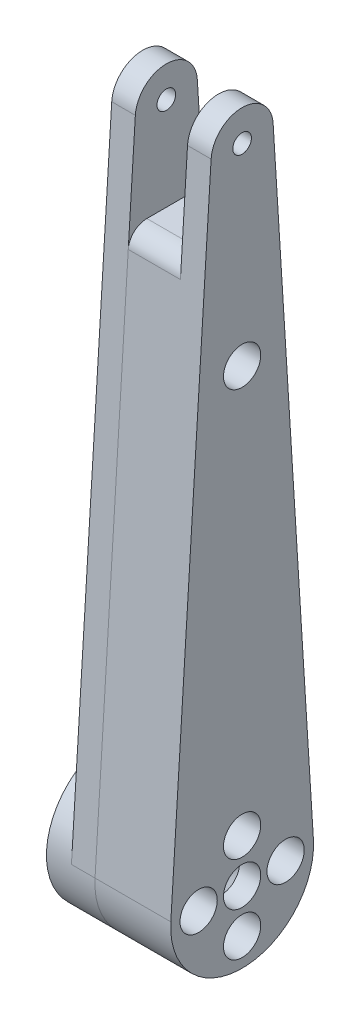
SolidWorks part; units mm, degrees
note: The reader was unsure of these and kept them because the rebuilt part matched: shared geometry of "Sketch1<4>", "Sketch1<5>".
ref_plane "Front Plane" through (0, 0, 0) normal (0, 0, 1) x (1, 0, 0)
ref_plane "Top Plane" through (0, 0, 0) normal (0, 1, 0) x (1, 0, 0)
ref_plane "Right Plane" through (0, 0, 0) normal (1, 0, 0) x (0, 0, -1)
sketch "Sketch1" plane through (0, 0, 0) normal (1, 0, 0) x (0, 0, -1)
  line L0 (11.4773, 0.7222) -> (4.9901, 103.814)
  line L1 (-4.9901, 103.814) -> (-11.4773, 0.7222)
  circle A0 centre (0, 0) radius 11.5
  circle A1 centre (0, 103.5) radius 5
  circle A2 centre (0, 0) radius 10.25
  circle A3 centre (0, 103.5) radius 1.5
  circle A4 centre (0, 0) radius 1.7
  dimension "D1" = 10
  dimension "D2" = 23
  dimension "D4" = 20.5
  dimension "D5" = 3.4
  dimension "D6" = 3
  dimension "D3" = 103.5
extrude "Boss-Extrude1" add sketch "Sketch1" along normal blind 16 contours A1 | A1 L1 A0 L0 | A0 A2 | A2
extrude "Boss-Extrude2" add sketch "Sketch1<4>" against normal blind 4 contours A0 A2
sketch "Sketch1<4>" plane through (0, 0, 0) normal (1, 0, 0) x (0, 0, -1) same geometry as "Sketch1"
extrude "Boss-Extrude3" add sketch "Sketch1<5>" against normal blind 2 contours A2 A4
sketch "Sketch1<5>" plane through (0, 0, 0) normal (1, 0, 0) x (0, 0, -1) same geometry as "Sketch1"
hole_wizard "CBORE for M3 Hex Socket Head Cap Screw1" positions "Sketch2" profile "Sketch3" counterbore size "M3" standard "ISO" end condition through all
sketch "Sketch2" plane through (16, 0, 0) normal (1, 0, 0) x (0, 0, -1)
  point P0 (0, 7)
  dimension "D1" = 7
sketch "Sketch3" plane through (16, 7, 0) normal (0, 1, 0) x (0, 0, -1)
  line L0 (0, 0) -> (0, 20)
  line L1 (0, 20) -> (1.7, 20)
  line L3 (1.7, 20) -> (1.7, 9.2)
  line L4 (1.7, 9.2) -> (3, 9.2)
  line L5 (3, 9.2) -> (3, 0)
  line L7 (3, 0) -> (0, 0)
  line L11 (0, -6.35) -> (0, 107.95) construction
  dimension "Thru Hole Dia." = 3.4
  dimension "Thru Hole Depth" = 20
  dimension "C'Bore Dia." = 6
  dimension "C'Bore Depth" = 9.2
chamfer "Chamfer1" distance 1.3 distance2 1.3 1 edges at (6.8, 7, -3)
pattern_circular "CirPattern2" count 4 over 360 about axis through (0, 0, 0) along (1, 0, 0) of "CBORE for M3 Hex Socket Head Cap Screw1", "Chamfer1"
sketch "Sketch4" plane through (16, 0, 0) normal (1, 0, 0) x (0, 0, -1)
  circle A0 centre (0, 0) radius 3
  circle A2 centre (0, 7) radius 3 construction
extrude "Cut-Extrude2" cut sketch "Sketch4" against normal blind 4.7
chamfer "Chamfer2" distance 1.3 distance2 1.3 1 edges at (11.3, 0, -3)
sketch "Sketch6" plane through (0, 0, 0) normal (0, 0, 1) x (1, 0, 0)
  line L1 (3.8, 108.5) -> (12.2, 108.5)
  line L2 (3.8, 108.5) -> (3.8, 88.5)
  line L3 (3.8, 88.5) -> (12.2, 88.5)
  line L4 (12.2, 108.5) -> (12.2, 88.5)
  line L5 (16, 108.5) -> (0, 108.5) construction
  point P8 (8, 108.5)
  dimension "D1" = 8.4
  dimension "D2" = 20
extrude "Cut-Extrude5" cut sketch "Sketch6" against normal through all both and the other way through all
fillet "Fillet1" radius 3 2 edges at (8, 88.5, -5.9538) (8, 88.5, 5.9538)
ref_plane "Plane1" through (3.8, 0, 0) normal (1, 0, 0) x (0, 0, -1)
split "Split1" trim tools "Plane1" bodies to split 111 resulting bodies 112 113
hole_wizard "CBORE for M3 Hex Socket Head Cap Screw2" positions "Sketch7" profile "Sketch8" counterbore size "M3" standard "ISO" end condition through all
sketch "Sketch7" plane through (16, 0, 0) normal (1, 0, 0) x (0, 0, -1)
  line L0 (3.1366, 88.5) -> (-3.1366, 88.5) construction
  point P0 (0, 72.5)
  dimension "D1" = 16
sketch "Sketch8" plane through (16, 72.5, 0) normal (0, 1, 0) x (0, 0, -1)
  line L0 (0, 0) -> (0, 20)
  line L1 (0, 20) -> (1.5, 20)
  line L3 (1.5, 20) -> (1.5, 8)
  line L4 (1.5, 8) -> (3, 8)
  line L5 (3, 8) -> (3, 0)
  line L7 (3, 0) -> (0, 0)
  line L11 (0, -6.35) -> (0, 107.95) construction
  dimension "Thru Hole Dia." = 3
  dimension "Thru Hole Depth" = 20
  dimension "C'Bore Dia." = 6
  dimension "C'Bore Depth" = 8
sketch "Sketch9" plane through (8, 0, 0) normal (1, 0, 0) x (0, 0, -1)
  circle A3 centre (0, 72.5) radius 1.7
  dimension "D1" = 3.4
extrude "Cut-Extrude6" cut sketch "Sketch9" against normal through all
chamfer "Chamfer3" distance 1.3 distance2 1.3 1 edges at (8, 72.5, -3)
other "Save Bodies1"
move or copy body "Body-Move/Copy1" [suppressed] bodies to move or copy 114 115
equation "\"D3@Sketch1\"=120-\"D2@Sketch1\"/2-\"D1@Sketch1\"/2"
